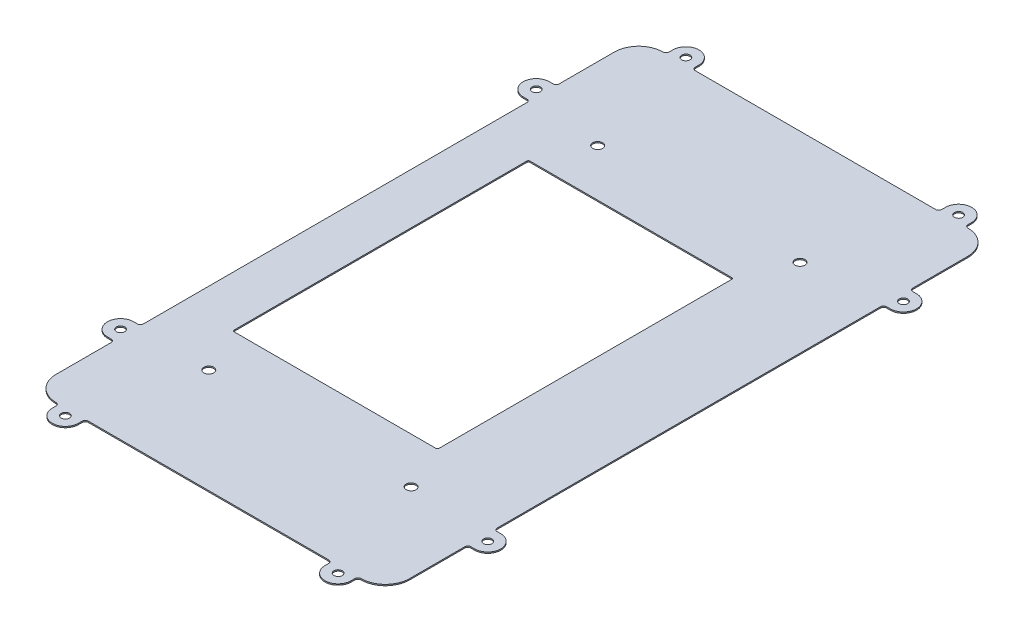
SolidWorks part; units mm, degrees
ref_plane "Front Plane" through (0, 0, 0) normal (0, 0, 1) x (1, 0, 0)
ref_plane "Top Plane" through (0, 0, 0) normal (0, 1, 0) x (1, 0, 0)
ref_plane "Right Plane" through (0, 0, 0) normal (1, 0, 0) x (0, 0, -1)
sketch "Sketch2" plane through (0, 0, 0) normal (0, 1, 0) x (1, 0, 0)
  line L1 (2.5, 0) -> (68, 0)
  line L2 (0, 2.5) -> (0, 97.5)
  line L3 (2.5, 100) -> (68, 100)
  line L4 (70.5, 2.5) -> (70.5, 97.5)
  arc A0 (0, 2.5) -> (2.5, 0) centre (2.5, 2.5) ccw
  arc A1 (68, 0) -> (70.5, 2.5) centre (68, 2.5) ccw
  arc A2 (70.5, 97.5) -> (68, 100) centre (68, 97.5) ccw
  arc A3 (2.5, 100) -> (0, 97.5) centre (2.5, 97.5) ccw
  point P7 (0, 0)
  point P10 (70.5, 0)
  point P13 (70.5, 100)
  point P16 (0, 100)
  dimension "D3" = 2.5
  dimension "D1" = 70.5
  dimension "D2" = 100
extrude "Base" add sketch "Sketch2" along normal blind 16.1
shell "Shell" thickness 2 removed face at (35.25, 16.1, -50) removed face at (35.25, 0, -50)
sketch "Board Location" plane through (0, 0, 0) normal (0, 1, 0) x (1, 0, 0)
  line L0 (39.5, 100) -> (39.5, 0) construction
  line L1 (68, 100) -> (2.5, 100) construction
  line L3 (0, 97.5) -> (0, 2.5) construction
  line L4 (2.5, 0) -> (68, 0) construction
  line L5 (0, 97.5) -> (0, 2.5) construction
  circle A0 centre (15, 74.25) radius 1.4
  circle A1 centre (15, 16.25) radius 1.4
  circle A2 centre (64, 16.25) radius 1.4
  circle A3 centre (64, 74.25) radius 1.4
  dimension "D1" = 2.8
  dimension "D2" = 25.75
  dimension "D3" = 83.75
  dimension "D4" = 15
  dimension "D5" = 39.5
sketch "Sketch19" plane through (0, 0, 0) normal (0, -1, 0) x (1, 0, 0)
  line L1 (-6.55, 46.74) -> (92.45, 46.74)
  line L2 (-14.43, 38.86) -> (-14.43, -142.34)
  line L3 (-6.55, -150.22) -> (92.45, -150.22)
  line L4 (100.33, 38.86) -> (100.33, -142.34)
  line L12 (2.5, -98) -> (68, -98)
  line L13 (68.5, -97.5) -> (68.5, -2.5)
  line L14 (68, -2) -> (2.5, -2)
  line L15 (2, -2.5) -> (2, -97.5)
  line L16 (2.5, -98) -> (68, -98)
  line L17 (68.5, -97.5) -> (68.5, -2.5)
  line L18 (68, -2) -> (2.5, -2)
  line L19 (2, -2.5) -> (2, -97.5)
  arc A0 (-14.43, -142.34) -> (-6.55, -150.22) centre (-6.55, -142.34) ccw
  arc A1 (92.45, -150.22) -> (100.33, -142.34) centre (92.45, -142.34) ccw
  arc A2 (100.33, 38.86) -> (92.45, 46.74) centre (92.45, 38.86) ccw
  arc A3 (-6.55, 46.74) -> (-14.43, 38.86) centre (-6.55, 38.86) ccw
  arc A12 (2, -97.5) -> (2.5, -98) centre (2.5, -97.5) ccw
  arc A13 (68, -98) -> (68.5, -97.5) centre (68, -97.5) ccw
  arc A14 (68.5, -2.5) -> (68, -2) centre (68, -2.5) ccw
  arc A15 (2.5, -2) -> (2, -2.5) centre (2.5, -2.5) ccw
  arc A16 (2, -97.5) -> (2.5, -98) centre (2.5, -97.5) ccw
  arc A17 (68, -98) -> (68.5, -97.5) centre (68, -97.5) ccw
  arc A18 (68.5, -2.5) -> (68, -2) centre (68, -2.5) ccw
  arc A19 (2.5, -2) -> (2, -2.5) centre (2.5, -2.5) ccw
  point P7 (-14.43, -150.22)
  point P12 (100.33, 46.74)
  point P15 (-14.43, 46.74)
  dimension "D5" = 7.88
  dimension "D1" = 62.99
  dimension "D2" = 29.43
  dimension "D3" = 114.76
  dimension "D4" = 196.96
  dimension "D6" = 0
extrude "Screen Base" add sketch "Sketch19" along normal blind 0.4
sketch "Sketch21" plane through (0, 0, 0) normal (0, 1, 0) x (1, 0, 0)
  line L0 (-6.55, 150.22) -> (92.45, 150.22) construction
  line L1 (92.45, -46.74) -> (-6.55, -46.74) construction
  line L2 (-14.43, -38.86) -> (-14.43, 142.34) construction
  line L3 (100.33, 142.34) -> (100.33, -38.86) construction
  circle A0 centre (9.15, 113.35) radius 1.6
  circle A1 centre (74.8, 113.35) radius 1.6
  circle A2 centre (74.8, -12.85) radius 1.6
  circle A3 centre (9.15, -12.85) radius 1.6
  dimension "D1" = 3.2
  dimension "D2" = 36.87
  dimension "D3" = 33.89
  dimension "D4" = 23.58
  dimension "D5" = 25.53
extrude "Leg Holes" cut sketch "Sketch21" against normal through all
sketch "Sketch22" plane through (0, 0, 0) normal (0, 1, 0) x (1, 0, 0)
  line L0 (-5.55, 152.42) -> (-5.55, 150.22)
  line L1 (-6.55, 150.22) -> (92.45, 150.22) construction
  line L2 (-5.55, 150.22) -> (2.95, 150.22)
  line L3 (2.95, 150.22) -> (2.95, 152.42)
  line L4 (82.95, 152.42) -> (82.95, 150.22)
  line L5 (82.95, 150.22) -> (91.45, 150.22)
  line L6 (91.45, 150.22) -> (91.45, 152.42)
  line L7 (-5.55, -48.94) -> (-5.55, -46.74)
  line L8 (92.45, -46.74) -> (-6.55, -46.74) construction
  line L9 (-5.55, -46.74) -> (2.95, -46.74)
  line L10 (2.95, -46.74) -> (2.95, -48.94)
  line L11 (82.95, -48.94) -> (82.95, -46.74)
  line L12 (82.95, -46.74) -> (91.45, -46.74)
  line L13 (91.45, -46.74) -> (91.45, -48.94)
  line L14 (-14.43, -38.86) -> (-14.43, 142.34) construction
  line L15 (100.33, 142.34) -> (100.33, -38.86) construction
  line L16 (-14.43, 51.74) -> (100.33, 51.74) construction
  line L22 (-14.43, 123.44) -> (-16.63, 123.44)
  line L23 (-14.43, 123.44) -> (-14.43, 114.94)
  line L24 (-14.43, 114.94) -> (-16.63, 114.94)
  line L26 (-14.43, -11.46) -> (-16.63, -11.46)
  line L27 (-14.43, -11.46) -> (-14.43, -19.96)
  line L28 (-14.43, -19.96) -> (-16.63, -19.96)
  line L30 (100.33, -11.46) -> (102.53, -11.46)
  line L31 (100.33, -11.46) -> (100.33, -19.96)
  line L32 (100.33, -19.96) -> (102.53, -19.96)
  line L34 (100.33, 123.44) -> (102.53, 123.44)
  line L35 (100.33, 123.44) -> (100.33, 114.94)
  line L36 (100.33, 114.94) -> (102.53, 114.94)
  arc A0 (-5.55, 152.42) -> (2.95, 152.42) centre (-1.3, 152.42) cw
  arc A1 (82.95, 152.42) -> (91.45, 152.42) centre (87.2, 152.42) cw
  arc A2 (-5.55, -48.94) -> (2.95, -48.94) centre (-1.3, -48.94) ccw
  arc A3 (82.95, -48.94) -> (91.45, -48.94) centre (87.2, -48.94) ccw
  arc A4 (-16.63, 123.44) -> (-16.63, 114.94) centre (-16.63, 119.19) ccw
  arc A5 (102.53, 123.44) -> (102.53, 114.94) centre (102.53, 119.19) cw
  arc A6 (102.53, -11.46) -> (102.53, -19.96) centre (102.53, -15.71) cw
  arc A7 (-16.63, -11.46) -> (-16.63, -19.96) centre (-16.63, -15.71) ccw
  dimension "D1" = 8.88
  dimension "D2" = 8.88
  dimension "D3" = 2.2
  dimension "D4" = 8.5
  dimension "D5" = 63.2
  dimension "D6" = 63.2
extrude "Screen Clamps" add sketch "Sketch22" against normal up to surface (0.4 mm away) up to face at (9.15, -0.4, 14.45)
fillet "Screen Clamp Fillets" radius 1 16 edges at (82.95, -0.2, 46.74) (-5.55, -0.2, 46.74) (2.95, -0.2, 46.74) (91.45, -0.2, 46.74) (2.95, -0.2, -150.22) (91.45, -0.2, -150.22) (82.95, -0.2, -150.22) (-5.55, -0.2, -150.22) (100.33, -0.2, -114.94) (100.33, -0.2, -123.44) (100.33, -0.2, 11.46) (100.33, -0.2, 19.96) (-14.43, -0.2, 19.96) (-14.43, -0.2, 11.46) (-14.43, -0.2, -123.44) (-14.43, -0.2, -114.94)
sketch "Sketch23" plane through (0, -0.4, 0) normal (0, 1, 0) x (1, 0, 0)
  circle A0 centre (-1.3, 152.42) radius 1.35
  circle A1 centre (87.2, 152.42) radius 1.35
  circle A2 centre (-1.3, -48.94) radius 1.35
  circle A3 centre (87.2, -48.94) radius 1.35
  arc A4 (2.95, 152.42) -> (-5.55, 152.42) centre (-1.3, 152.42) ccw construction
  arc A5 (91.45, 152.42) -> (82.95, 152.42) centre (87.2, 152.42) ccw construction
  arc A6 (-5.55, -48.94) -> (2.95, -48.94) centre (-1.3, -48.94) ccw construction
  arc A7 (82.95, -48.94) -> (91.45, -48.94) centre (87.2, -48.94) ccw construction
  circle A8 centre (-16.63, 119.19) radius 1.35
  circle A9 centre (102.53, 119.19) radius 1.35
  circle A10 centre (102.53, -15.71) radius 1.35
  circle A11 centre (-16.63, -15.71) radius 1.35
  dimension "D1" = 2.7
extrude "Cut-Extrude1" cut sketch "Sketch23" along normal up to surface (0.4 mm away) up to face at (9.15, 0, 14.45)
sketch "Sketch24" plane through (0, 0, 0) normal (0, 1, 0) x (1, 0, 0)
  line L63 (-16.63, 114.94) -> (-15.43, 114.94)
  line L64 (-15.43, 123.44) -> (-16.63, 123.44)
  line L65 (-14.43, 142.34) -> (-14.43, 124.44)
  line L66 (-5.55, 152.42) -> (-5.55, 151.22)
  line L67 (2.95, 151.22) -> (2.95, 152.42)
  line L68 (81.95, 150.22) -> (3.95, 150.22)
  line L69 (82.95, 152.42) -> (82.95, 151.22)
  line L70 (91.45, 151.22) -> (91.45, 152.42)
  line L71 (100.33, 124.44) -> (100.33, 142.34)
  line L72 (102.53, 123.44) -> (101.33, 123.44)
  line L73 (101.33, 114.94) -> (102.53, 114.94)
  line L74 (100.33, -10.46) -> (100.33, 113.94)
  line L75 (102.53, -11.46) -> (101.33, -11.46)
  line L76 (101.33, -19.96) -> (102.53, -19.96)
  line L77 (100.33, -38.86) -> (100.33, -20.96)
  line L78 (91.45, -48.94) -> (91.45, -47.74)
  line L79 (82.95, -47.74) -> (82.95, -48.94)
  line L80 (3.95, -46.74) -> (81.95, -46.74)
  line L81 (-14.43, 113.94) -> (-14.43, -10.46)
  line L82 (-15.43, -11.46) -> (-16.63, -11.46)
  line L83 (-16.63, -19.96) -> (-15.43, -19.96)
  line L84 (-14.43, -20.96) -> (-14.43, -38.86)
  line L85 (-5.55, -47.74) -> (-5.55, -48.94)
  line L86 (2.95, -48.94) -> (2.95, -47.74)
  line L87 (-16.63, 114.94) -> (-15.43, 114.94)
  line L88 (-15.43, 123.44) -> (-16.63, 123.44)
  line L89 (-14.43, 142.34) -> (-14.43, 124.44)
  line L90 (-5.55, 152.42) -> (-5.55, 151.22)
  line L91 (2.95, 151.22) -> (2.95, 152.42)
  line L92 (81.95, 150.22) -> (3.95, 150.22)
  line L93 (82.95, 152.42) -> (82.95, 151.22)
  line L94 (91.45, 151.22) -> (91.45, 152.42)
  line L95 (100.33, 124.44) -> (100.33, 142.34)
  line L96 (102.53, 123.44) -> (101.33, 123.44)
  line L97 (101.33, 114.94) -> (102.53, 114.94)
  line L98 (100.33, -10.46) -> (100.33, 113.94)
  line L99 (102.53, -11.46) -> (101.33, -11.46)
  line L100 (101.33, -19.96) -> (102.53, -19.96)
  line L101 (100.33, -38.86) -> (100.33, -20.96)
  line L102 (91.45, -48.94) -> (91.45, -47.74)
  line L103 (82.95, -47.74) -> (82.95, -48.94)
  line L104 (3.95, -46.74) -> (81.95, -46.74)
  line L105 (-14.43, 113.94) -> (-14.43, -10.46)
  line L106 (-15.43, -11.46) -> (-16.63, -11.46)
  line L107 (-16.63, -19.96) -> (-15.43, -19.96)
  line L108 (-14.43, -20.96) -> (-14.43, -38.86)
  line L109 (-5.55, -47.74) -> (-5.55, -48.94)
  line L110 (2.95, -48.94) -> (2.95, -47.74)
  arc A5 (100.33, 124.44) -> (101.33, 123.44) centre (101.33, 124.44) ccw construction
  arc A73 (-14.43, 113.94) -> (-15.43, 114.94) centre (-15.43, 113.94) ccw
  arc A74 (-16.63, 123.44) -> (-16.63, 114.94) centre (-16.63, 119.19) ccw
  arc A75 (-15.43, 123.44) -> (-14.43, 124.44) centre (-15.43, 124.44) ccw
  arc A76 (-6.55, 150.22) -> (-14.43, 142.34) centre (-6.55, 142.34) ccw
  arc A77 (-6.55, 150.22) -> (-5.55, 151.22) centre (-6.55, 151.22) ccw
  arc A78 (2.95, 152.42) -> (-5.55, 152.42) centre (-1.3, 152.42) ccw
  arc A79 (2.95, 151.22) -> (3.95, 150.22) centre (3.95, 151.22) ccw
  arc A80 (81.95, 150.22) -> (82.95, 151.22) centre (81.95, 151.22) ccw
  arc A81 (91.45, 152.42) -> (82.95, 152.42) centre (87.2, 152.42) ccw
  arc A82 (91.45, 151.22) -> (92.45, 150.22) centre (92.45, 151.22) ccw
  arc A83 (100.33, 142.34) -> (92.45, 150.22) centre (92.45, 142.34) ccw
  arc A84 (100.33, 124.44) -> (101.33, 123.44) centre (101.33, 124.44) ccw
  arc A85 (102.53, 114.94) -> (102.53, 123.44) centre (102.53, 119.19) ccw
  arc A86 (101.33, 114.94) -> (100.33, 113.94) centre (101.33, 113.94) ccw
  arc A87 (100.33, -10.46) -> (101.33, -11.46) centre (101.33, -10.46) ccw
  arc A88 (102.53, -19.96) -> (102.53, -11.46) centre (102.53, -15.71) ccw
  arc A89 (101.33, -19.96) -> (100.33, -20.96) centre (101.33, -20.96) ccw
  arc A90 (92.45, -46.74) -> (100.33, -38.86) centre (92.45, -38.86) ccw
  arc A91 (92.45, -46.74) -> (91.45, -47.74) centre (92.45, -47.74) ccw
  arc A92 (82.95, -48.94) -> (91.45, -48.94) centre (87.2, -48.94) ccw
  arc A93 (82.95, -47.74) -> (81.95, -46.74) centre (81.95, -47.74) ccw
  arc A94 (-15.43, -11.46) -> (-14.43, -10.46) centre (-15.43, -10.46) ccw
  arc A95 (-16.63, -11.46) -> (-16.63, -19.96) centre (-16.63, -15.71) ccw
  arc A96 (-14.43, -20.96) -> (-15.43, -19.96) centre (-15.43, -20.96) ccw
  arc A97 (-14.43, -38.86) -> (-6.55, -46.74) centre (-6.55, -38.86) ccw
  arc A98 (-5.55, -47.74) -> (-6.55, -46.74) centre (-6.55, -47.74) ccw
  arc A99 (-5.55, -48.94) -> (2.95, -48.94) centre (-1.3, -48.94) ccw
  arc A100 (3.95, -46.74) -> (2.95, -47.74) centre (3.95, -47.74) ccw
  arc A101 (-14.43, 113.94) -> (-15.43, 114.94) centre (-15.43, 113.94) ccw
  arc A102 (-16.63, 123.44) -> (-16.63, 114.94) centre (-16.63, 119.19) ccw
  arc A103 (-15.43, 123.44) -> (-14.43, 124.44) centre (-15.43, 124.44) ccw
  arc A104 (-6.55, 150.22) -> (-14.43, 142.34) centre (-6.55, 142.34) ccw
  arc A105 (-6.55, 150.22) -> (-5.55, 151.22) centre (-6.55, 151.22) ccw
  arc A106 (2.95, 152.42) -> (-5.55, 152.42) centre (-1.3, 152.42) ccw
  arc A107 (2.95, 151.22) -> (3.95, 150.22) centre (3.95, 151.22) ccw
  arc A108 (81.95, 150.22) -> (82.95, 151.22) centre (81.95, 151.22) ccw
  arc A109 (91.45, 152.42) -> (82.95, 152.42) centre (87.2, 152.42) ccw
  arc A110 (91.45, 151.22) -> (92.45, 150.22) centre (92.45, 151.22) ccw
  arc A111 (100.33, 142.34) -> (92.45, 150.22) centre (92.45, 142.34) ccw
  arc A112 (100.33, 124.44) -> (101.33, 123.44) centre (101.33, 124.44) ccw
  arc A113 (102.53, 114.94) -> (102.53, 123.44) centre (102.53, 119.19) ccw
  arc A114 (101.33, 114.94) -> (100.33, 113.94) centre (101.33, 113.94) ccw
  arc A115 (100.33, -10.46) -> (101.33, -11.46) centre (101.33, -10.46) ccw
  arc A116 (102.53, -19.96) -> (102.53, -11.46) centre (102.53, -15.71) ccw
  arc A117 (101.33, -19.96) -> (100.33, -20.96) centre (101.33, -20.96) ccw
  arc A118 (92.45, -46.74) -> (100.33, -38.86) centre (92.45, -38.86) ccw
  arc A119 (92.45, -46.74) -> (91.45, -47.74) centre (92.45, -47.74) ccw
  arc A120 (82.95, -48.94) -> (91.45, -48.94) centre (87.2, -48.94) ccw
  arc A121 (82.95, -47.74) -> (81.95, -46.74) centre (81.95, -47.74) ccw
  arc A122 (-15.43, -11.46) -> (-14.43, -10.46) centre (-15.43, -10.46) ccw
  arc A123 (-16.63, -11.46) -> (-16.63, -19.96) centre (-16.63, -15.71) ccw
  arc A124 (-14.43, -20.96) -> (-15.43, -19.96) centre (-15.43, -20.96) ccw
  arc A125 (-14.43, -38.86) -> (-6.55, -46.74) centre (-6.55, -38.86) ccw
  arc A126 (-5.55, -47.74) -> (-6.55, -46.74) centre (-6.55, -47.74) ccw
  arc A127 (-5.55, -48.94) -> (2.95, -48.94) centre (-1.3, -48.94) ccw
  arc A128 (3.95, -46.74) -> (2.95, -47.74) centre (3.95, -47.74) ccw
  dimension "D1" = 0
extrude "Cut-Extrude2" cut sketch "Sketch24" along normal through all
